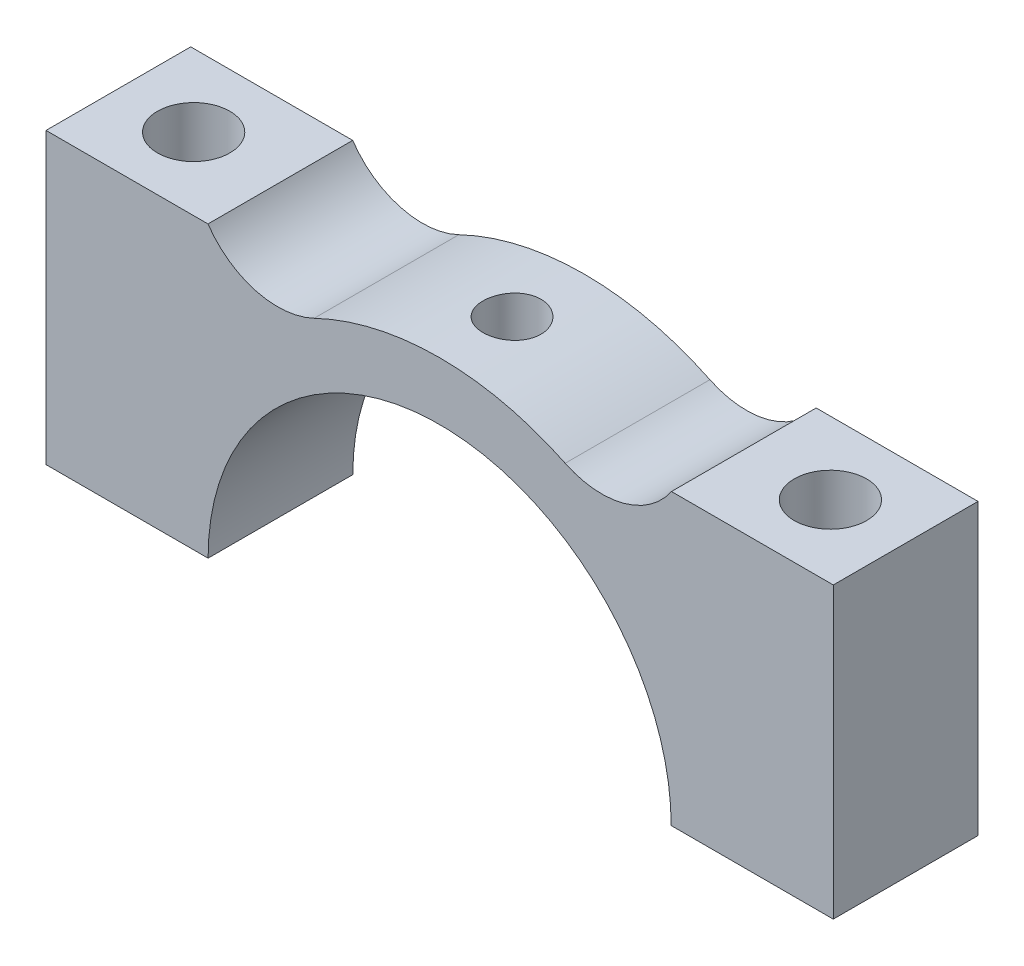
SolidWorks part; units mm, degrees
ref_plane "Front Plane" through (0, 0, 0) normal (0, 0, 1) x (1, 0, 0)
ref_plane "Top Plane" through (0, 0, 0) normal (0, 1, 0) x (1, 0, 0)
ref_plane "Right Plane" through (0, 0, 0) normal (1, 0, 0) x (0, 0, -1)
sketch "Sketch2" plane through (0, 0, 0) normal (0, 0, 1) x (1, 0, 0)
  line L1 (-8, 0) -> (-13.6, 0)
  line L2 (-13.6, 0) -> (-13.6, 10)
  line L3 (-13.6, 10) -> (-8, 10)
  line L4 (-8, 10) -> (-8, 0)
  line L6 (8, 0) -> (13.6, 0)
  line L7 (13.6, 0) -> (13.6, 10)
  line L8 (13.6, 10) -> (8, 10)
  line L9 (8, 10) -> (8, 0)
  circle A0 centre (0, 0) radius 8
  circle A1 centre (0, 0) radius 10
  circle A2 centre (-5.5966, 11.6315) radius 2.9079
  circle A3 centre (5.6, 11.6315) radius 2.9094
  spline S0 degree 1 poles (-8, 10) (0, 10) knots 0 0 1 1
  dimension "D1" = 16
  dimension "D2" = 20
  dimension "D5" = 10
  dimension "D7" = 5.8158
  dimension "D3" = 5.6
  dimension "D4" = 10
  dimension "D6" = 5.6
extrude "Boss-Extrude1" add sketch "Sketch2" along normal blind 5 contours A2 L3 L2 L1 A1 L4 | A2 L4 A1 | L4 A1 L1 | L9 A1 L4 A0 | L6 A1 L9 | L9 A1 L6 L7 L8 | A3 A1 L9 region at (-8.8073, 2.2834, 0) region at (-7.8113, 3, 0) region at (-11.1406, 5.4644, 0) region at (-7.0988, 8.1255, 0) region at (8.8073, 2.2834, 0) region at (11.1406, 5.4644, 0) region at (7.0992, 8.1233, 0)
sketch "Sketch3" plane through (0, 10, 0) normal (0, 1, 0) x (1, 0, 0)
  circle A0 centre (-10.9989, -2.5) radius 1.25
  circle A1 centre (11.0011, -2.5) radius 1.25
  dimension "D3" = 2.5
  dimension "D4" = 2.5
extrude "Cut-Extrude1" cut sketch "Sketch3" against normal through all and the other way blind 300
sketch "Sketch4" plane through (0, 10, 0) normal (0, 1, 0) x (1, 0, 0)
  circle A0 centre (0, -2.5) radius 1
extrude "Cut-Extrude2" cut sketch "Sketch4" against normal through all
